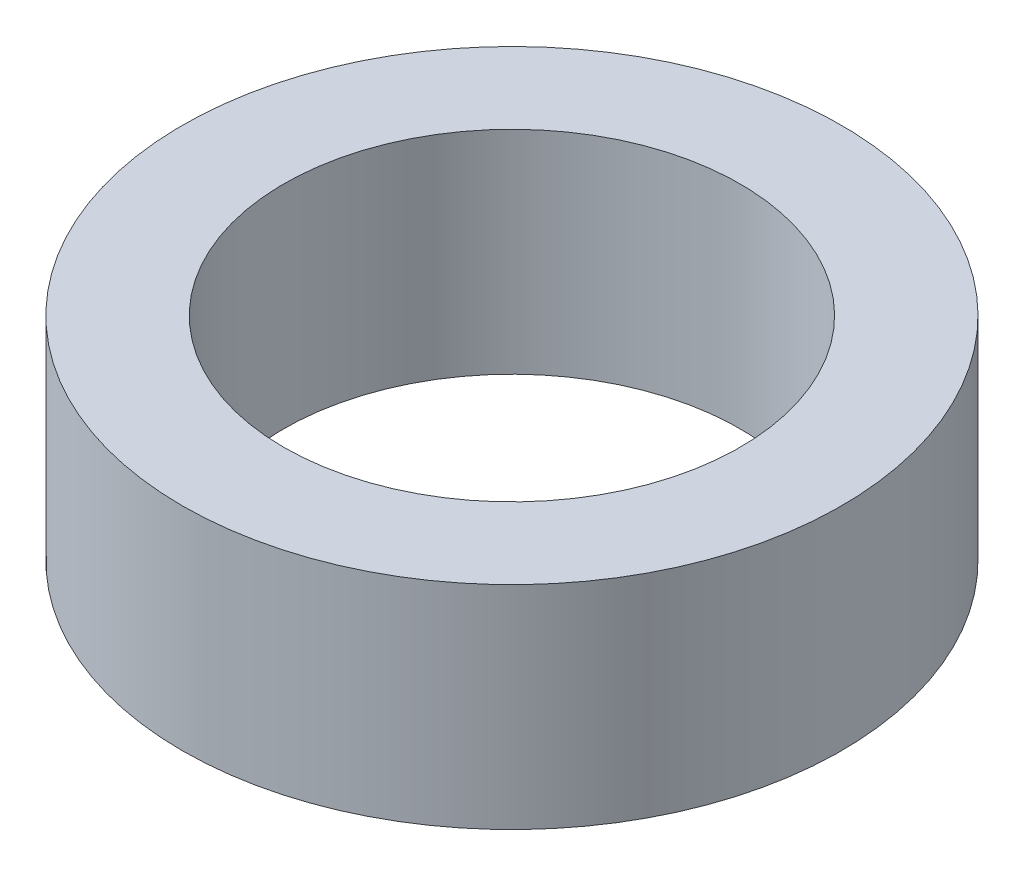
SolidWorks part; units mm, degrees
ref_plane "Plan de face" through (0, 0, 0) normal (0, 0, 1) x (1, 0, 0)
ref_plane "Plan de dessus" through (0, 0, 0) normal (0, 1, 0) x (1, 0, 0)
ref_plane "Plan de droite" through (0, 0, 0) normal (1, 0, 0) x (0, 0, -1)
sketch "Esquisse1" plane through (0, 0, 0) normal (0, 1, 0) x (1, 0, 0)
  circle A0 centre (0, 0) radius 2.25
  circle A1 centre (0, 0) radius 3.25
  dimension "D1" = 4.5
  dimension "D2" = 6.5
extrude "Boss.-Extru.1" add sketch "Esquisse1" along normal blind 2.0918
